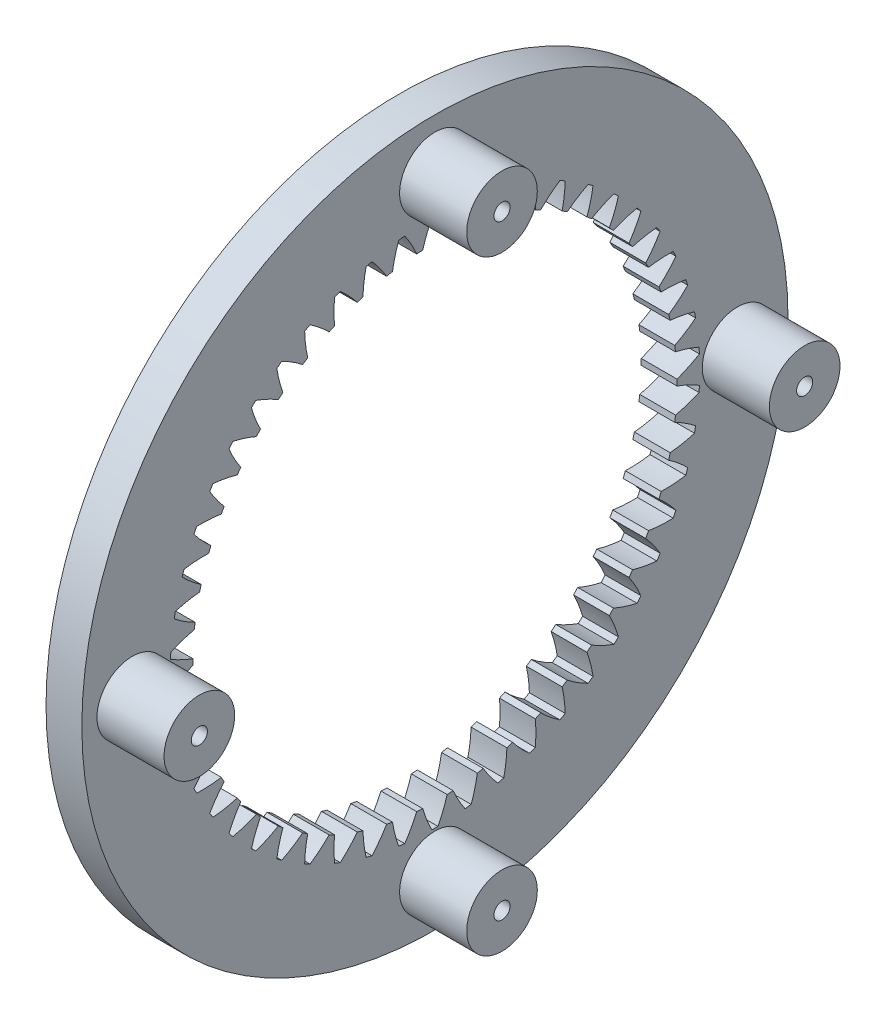
SolidWorks part; units mm, degrees
ref_plane "Plane1" through (0, 0, 0) normal (0, 0, 1) x (1, 0, 0)
ref_plane "Plane2" through (0, 0, 0) normal (0, 1, 0) x (1, 0, 0)
ref_plane "Plane3" through (0, 0, 0) normal (1, 0, 0) x (0, 0, -1)
other "Configuration Table"
sketch "HoldingSke" plane through (0, 0, 0) normal (0, 1, 0) x (1, 0, 0)
  line L0 (0, 0) -> (0.3214, -0.383)
  line L1 (-15, 0) -> (100, 0) construction
  line L2 (0, 0) -> (-2.1039, 2.3779)
  line L3 (0, 0) -> (-11.863, 4.5341)
  line L4 (0, 0) -> (5.5511, 6.6156)
  line L5 (0, 0) -> (-23.7986, -8.8762)
  line L6 (0, 0) -> (-10.5278, -7.1032)
  line L7 (-2.1039, 2.3779) -> (3.3635, 27.1825)
  line L8 (-76.2, 4.3779) -> (-54.61, 4.3779)
  line L9 (-71.009, 38.7566) -> (-53.1078, 45.2721)
  line L10 (-76.2, 71.12) -> (104.1128, 71.12)
  line L11 (0, 0) -> (-15.2, 0)
  line L12 (-76.2, 101.6) -> (-76.133, 101.6)
  line L13 (24.9733, 27.94) -> (52.9518, 28.4284)
  line L14 (24.9733, 27.94) -> (24.9743, 27.94)
  line L15 (24.9733, 27.94) -> (100.4006, 29.5858)
  circle A0 centre (0, 0) radius 70
  circle A1 centre (0, 0) radius 12.7
  circle A2 centre (0, 0) radius 12.7
  dimension "Num_teeth" = 50
  dimension "Pitch_radius" = 180.3128
  dimension "Width" = 15.2
  dimension "Diameter" = 140
sketch "BasProSke" plane through (0, 0, 0) normal (0, 1, 0) x (1, 0, 0)
  line L0 (-10, 0) -> (60, 0) construction
  line L1 (0, 48) -> (0, 70)
  line L2 (0, 48) -> (15.2, 48)
  line L3 (15.2, 48) -> (15.2, 70)
  line L4 (15.2, 70) -> (0, 70)
  dimension "Thickness" = 15.2
  dimension "Diameter" = 140
revolve "Base-Revolve" add sketch "BasProSke" angle 360 about L0
sketch "TooCutSke" plane through (0, 0, 0) normal (1, 0, 0) x (0, 0, -1)
  line L3 (1.738, 49.9698) -> (1.738, 53.6633) construction
  line L4 (0, 0) -> (0, 59.563) construction
  line L5 (0, 0) -> (-4.2903, 68.1927) construction
  line L6 (-21.6015, 41.0107) -> (35.113, 44.5789) construction
  circle A0 centre (0, 0) radius 50 construction
  circle A1 centre (0, 0) radius 52.501 construction
  circle A2 centre (0, 0) radius 42.2862 construction
  circle A3 centre (0, 0) radius 47.9746 construction
  arc A4 (2.4267, 47.9132) -> (0.6033, 52.4975) centre (-21.6015, 41.0107) ccw
  arc A5 (2.4267, 47.9132) -> (-2.4267, 47.9132) centre (0, 0) ccw
  arc A6 (0.6033, 52.4975) -> (-0.6033, 52.4975) centre (0, 0) ccw
  arc A7 (-0.6033, 52.4975) -> (-2.4267, 47.9132) centre (21.6015, 41.0107) ccw
extrude "ToothCut" cut sketch "TooCutSke" along normal through all
fillet "Breaks" [suppressed] radius 0.2
fillet "RootFillets" [suppressed] radius 0.501
pattern_circular "TeethCuts" count 50 every 7.2 about axis through (-10, 0, 0) along (1, 0, 0) of "RootFillets", "Breaks", "ToothCut"
sketch "Sketch1" plane through (15.2, 0, 0) normal (1, 0, 0) x (0, 0, -1)
  circle A0 centre (0, 0) radius 60
  circle A1 centre (0, 60) radius 1.6
  circle A2 centre (60, 0) radius 1.6
  circle A3 centre (0, -60) radius 1.6
  circle A4 centre (-60, 0) radius 1.6
  point P14 (0, 0)
  dimension "D1" = 4
extrude "Cut-Extrude1" cut sketch "Sketch1" against normal blind 16 contours A0 A1 | A0 A1 | A2 | A3 | A4 region at (15.2, 59.3171, 0) region at (15.2, 60.6752, 0)
sketch "Sketch11" plane through (0, 0, 0) normal (-1, 0, 0) x (0, 0, 1)
  line L0 (63.2332, 0) -> (61.6166, 2.8)
  line L1 (0, 63.2332) -> (-2.8, 61.6166)
  line L2 (-2.8, 61.6166) -> (-2.8, 58.3834)
  line L3 (-2.8, 58.3834) -> (0, 56.7668)
  line L4 (0, 56.7668) -> (2.8, 58.3834)
  line L5 (2.8, 58.3834) -> (2.8, 61.6166)
  line L6 (2.8, 61.6166) -> (0, 63.2332)
  line L7 (61.6166, 2.8) -> (58.3834, 2.8)
  line L8 (58.3834, 2.8) -> (56.7668, 0)
  line L9 (56.7668, 0) -> (58.3834, -2.8)
  line L10 (58.3834, -2.8) -> (61.6166, -2.8)
  line L11 (61.6166, -2.8) -> (63.2332, 0)
  line L12 (0, -63.2332) -> (2.8, -61.6166)
  line L13 (2.8, -61.6166) -> (2.8, -58.3834)
  line L14 (2.8, -58.3834) -> (0, -56.7668)
  line L15 (0, -56.7668) -> (-2.8, -58.3834)
  line L16 (-2.8, -58.3834) -> (-2.8, -61.6166)
  line L17 (-2.8, -61.6166) -> (0, -63.2332)
  line L18 (-63.2332, 0) -> (-61.6166, -2.8)
  line L19 (-61.6166, -2.8) -> (-58.3834, -2.8)
  line L20 (-58.3834, -2.8) -> (-56.7668, 0)
  line L21 (-56.7668, 0) -> (-58.3834, 2.8)
  line L22 (-58.3834, 2.8) -> (-61.6166, 2.8)
  line L23 (-61.6166, 2.8) -> (-63.2332, 0)
  circle A0 centre (0, 60) radius 2.8 construction
  point P30 (0, 0)
  dimension "D1" = 4
extrude "Cut-Extrude11" cut sketch "Sketch11" against normal blind 3
sketch "Sketch12" plane through (15.2, 0, 0) normal (1, 0, 0) x (0, 0, -1)
  circle A1 centre (0, 0) radius 70
  circle A2 centre (0, 0) radius 70
  dimension "D1" = 0
extrude "Cut-Extrude12" cut sketch "Sketch12" against normal blind 8.1
sketch "Sketch13" plane through (7.1, 0, 0) normal (1, 0, 0) x (0, 0, -1)
  circle A0 centre (0, 60) radius 7
  circle A1 centre (0, 60) radius 1.6 construction
  circle A2 centre (0, 60) radius 1.6
  circle A3 centre (60, 0) radius 7
  circle A4 centre (60, 0) radius 1.6
  circle A5 centre (0, -60) radius 7
  circle A6 centre (0, -60) radius 1.6
  circle A7 centre (-60, 0) radius 7
  circle A8 centre (-60, 0) radius 1.6
  point P21 (0, 0)
  dimension "D1" = 4
extrude "Boss-Extrude1" add sketch "Sketch13" along normal blind 13.3
sketch "Sketch14" plane through (3, 0, 0) normal (-1, 0, 0) x (0, 0, 1)
  line L0 (-2.8, 61.6166) -> (-2.8, 58.3834) construction
  line L1 (-2.8, 58.3834) -> (0, 56.7668) construction
  line L2 (0, 56.7668) -> (2.8, 58.3834) construction
  line L3 (2.8, 58.3834) -> (2.8, 61.6166) construction
  line L4 (2.8, 61.6166) -> (0, 63.2332) construction
  line L5 (0, 63.2332) -> (-2.8, 61.6166) construction
  line L6 (-2.8, 61.6166) -> (-2.8, 58.3834)
  line L7 (-2.8, 58.3834) -> (0, 56.7668)
  line L8 (0, 56.7668) -> (2.8, 58.3834)
  line L9 (2.8, 58.3834) -> (2.8, 61.6166)
  line L10 (2.8, 61.6166) -> (0, 63.2332)
  line L11 (0, 63.2332) -> (-2.8, 61.6166)
  line L12 (61.6166, -2.8) -> (63.2332, 0)
  line L13 (63.2332, 0) -> (61.6166, 2.8)
  line L14 (61.6166, 2.8) -> (58.3834, 2.8)
  line L15 (58.3834, 2.8) -> (56.7668, 0)
  line L16 (56.7668, 0) -> (58.3834, -2.8)
  line L17 (58.3834, -2.8) -> (61.6166, -2.8)
  line L18 (-2.8, -61.6166) -> (0, -63.2332)
  line L19 (0, -63.2332) -> (2.8, -61.6166)
  line L20 (2.8, -61.6166) -> (2.8, -58.3834)
  line L21 (2.8, -58.3834) -> (0, -56.7668)
  line L22 (0, -56.7668) -> (-2.8, -58.3834)
  line L23 (-2.8, -58.3834) -> (-2.8, -61.6166)
  line L24 (-61.6166, 2.8) -> (-63.2332, 0)
  line L25 (-63.2332, 0) -> (-61.6166, -2.8)
  line L26 (-61.6166, -2.8) -> (-58.3834, -2.8)
  line L27 (-58.3834, -2.8) -> (-56.7668, 0)
  line L28 (-56.7668, 0) -> (-58.3834, 2.8)
  line L29 (-58.3834, 2.8) -> (-61.6166, 2.8)
  circle A0 centre (0, 60) radius 1.6 construction
  circle A1 centre (0, 60) radius 1.6
  circle A2 centre (60, 0) radius 1.6
  circle A3 centre (0, -60) radius 1.6
  circle A4 centre (-60, 0) radius 1.6
  point P36 (0, 0)
  dimension "D1" = 4
extrude "Cut-Extrude13" cut sketch "Sketch14" against normal blind 4.4
equation "' \"Module@HoldingSke\" = 6.35"
equation "' \"Num_teeth@HoldingSke\" = 24"
equation "' \"Ap@HoldingSke\" =  14.5"
equation "' \"Ap@HoldingSke\" = 14.5"
equation "' \"Width@HoldingSke\" = 12"
equation "' \"Diameter@HoldingSke\" = 8 * 25.4"
equation "' \"Show_teeth@HoldingSke\" = 100"
equation "' \"Backlash@HoldingSke\" = 0.009 * 25.4"
equation "' \"Addendum_fac@HoldingSke\" = 1.0"
equation "' \"Dedendum_fac@HoldingSke\" = 1.25"
equation "' \"Dedendum_add@HoldingSke\" = 0.00005 * 25.4"
equation "' \"Clearance_fac@HoldingSke\" = 0.25"
equation "\"Pitch@HoldingSke\" = 1 / \"Module@HoldingSke\" "
equation "\"Overcut_dia@TooCutSke\" = (\"Num_teeth@HoldingSke\" - 2 * \"Addendum_fac@HoldingSke\") / \"Pitch@HoldingSke\" - 0.002 * 25.4"
equation "\"Pitch_dia@TooCutSke\" = \"Num_teeth@HoldingSke\" / \"Pitch@HoldingSke\""
equation "\"Base_dia@TooCutSke\" = \"Num_teeth@HoldingSke\" / \"Pitch@HoldingSke\" * cos((\"Ap@HoldingSke\"  * 3.14159265 / 180)) * 0.90"
equation "\"Root_dia@TooCutSke\" = \"Num_teeth@HoldingSke\"  / \"Pitch@HoldingSke\" + 2 *  \"Dedendum_fac@HoldingSke\"/ \"Pitch@HoldingSke\" + \"Dedendum_add@HoldingSke\" * 2"
equation "\"Half_ang@TooCutSke\" = 180 / \"Num_teeth@HoldingSke\""
equation "\"Half_CT@TooCutSke\" = \"Num_teeth@HoldingSke\" / \"Pitch@HoldingSke\" * sin((3.14159265 / 2 / \"Num_teeth@HoldingSke\")) / 2 + 10 * \"Backlash@HoldingSke\" / 4"
equation "\"Flank_rad@TooCutSke\" = \"Num_teeth@HoldingSke\" / \"Pitch@HoldingSke\" / 4"
equation "\"Radius@RootFillets\"= \"Clearance_fac@HoldingSke\" / \"Pitch@HoldingSke\" + \"Dedendum_add@HoldingSke\""
equation "\"Break_rad@Breaks\" = 0.02 / \"Pitch@HoldingSke\" * 5"
equation "\"Num_teeth@TeethCuts\" = int( \"Show_teeth@HoldingSke\" ) + 1"
equation "\"Num_teeth@TeethCuts\" = ((sgn( \"Num_teeth@TeethCuts\" - \"Num_teeth@HoldingSke\" )-1)*( \"Num_teeth@TeethCuts\" - \"Num_teeth@HoldingSke\" ))/-2+ \"Num_teeth@HoldingSke\""
equation "\"Num_teeth@TeethCuts\" = ((sgn( \"Num_teeth@TeethCuts\" - 2.0)+1)*( \"Num_teeth@TeethCuts\" - 2.0))/2 +2.0"
equation "\"Angle@TeethCuts\" = 360.0 / \"Num_teeth@HoldingSke\""
equation "\"Diameter@BasProSke\" = \"Num_teeth@HoldingSke\"  / \"Pitch@HoldingSke\" + 2 *  \"Dedendum_fac@HoldingSke\"/ \"Pitch@HoldingSke\" + \"Dedendum_add@HoldingSke\" * 2 + 0.002 * 25.4"
equation "\"Diameter@BasProSke\" = ((sgn( \"Diameter@BasProSke\"  - \"Diameter@HoldingSke\" )+1)*( \"Diameter@BasProSke\"  - \"Diameter@HoldingSke\" ))/2 + \"Diameter@HoldingSke\""
equation "\"Inside_diameter@BasProSke\" =  (\"Num_teeth@HoldingSke\" - 2 * \"Addendum_fac@HoldingSke\") / \"Pitch@HoldingSke\" "
equation "\"Thickness@BasProSke\"  = \"Width@HoldingSke\""
